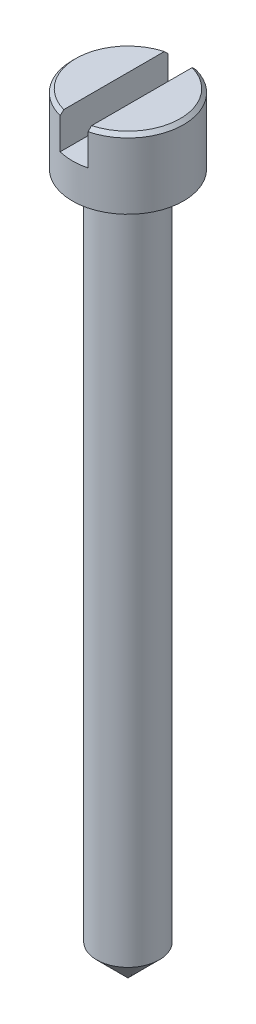
SolidWorks part; units mm, degrees
ref_plane "Спереди" through (0, 0, 0) normal (0, 0, 1) x (1, 0, 0)
ref_plane "Сверху" through (0, 0, 0) normal (0, 1, 0) x (1, 0, 0)
ref_plane "Справа" through (0, 0, 0) normal (1, 0, 0) x (0, 0, -1)
sketch "Эскиз1" plane through (0, 0, 0) normal (0, 0, 1) x (1, 0, 0)
  line L0 (0, 0) -> (0, -36.2649) construction
  line L1 (0, 0) -> (0, 221.5)
  line L2 (0, 221.5) -> (16, 221.5)
  line L3 (16, 221.5) -> (16, 201.5)
  line L4 (16, 201.5) -> (9, 201.5)
  line L5 (9, 201.5) -> (9, 0)
  line L6 (9, 0) -> (0, 0)
  dimension "D1" = 18
  dimension "D2" = 32
  dimension "D3" = 201.5
  dimension "D4" = 20
revolve "Повернуть1" add sketch "Эскиз1" angle 360 about L0
chamfer "Фаска1" distance 9 angle 45 1 edges at (0, 0, 9)
sketch "Эскиз2" plane through (0, 0, 0) normal (0, 0, 1) x (1, 0, 0)
  line L0 (16, 221.5) -> (-16, 221.5) construction
  line L1 (-4, 221.5) -> (4, 221.5)
  line L2 (-4, 221.5) -> (-4, 211.5)
  line L3 (-4, 211.5) -> (4, 211.5)
  line L4 (4, 221.5) -> (4, 211.5)
  dimension "D1" = 8
  dimension "D2" = 4
  dimension "D3" = 10
extrude "Вырез-Вытянуть1" cut sketch "Эскиз2" against normal through all and the other way through all
chamfer "Фаска2" distance 1 angle 45 2 edges at (-16, 221.5, 0) (16, 221.5, 0)
